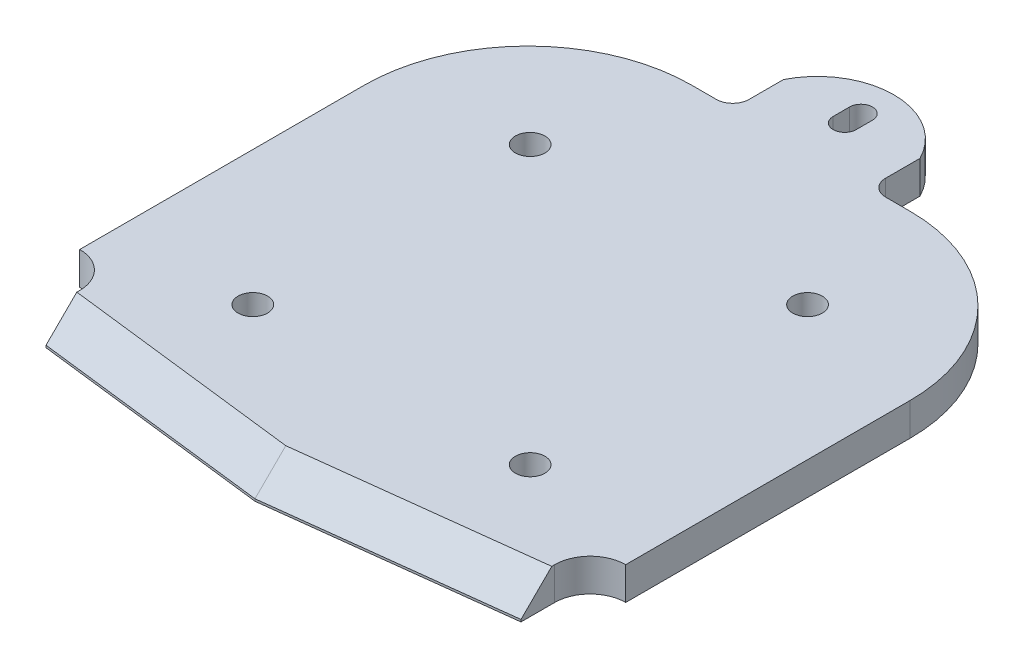
SolidWorks part; units mm, degrees
note: The reader was unsure of these and kept them because the rebuilt part matched: shared geometry of "Sketch2<2>".
ref_plane "Front Plane" through (0, 0, 0) normal (0, 0, 1) x (1, 0, 0)
ref_plane "Top Plane" through (0, 0, 0) normal (0, 1, 0) x (1, 0, 0)
ref_plane "Right Plane" through (0, 0, 0) normal (1, 0, 0) x (0, 0, -1)
sketch "Sketch1" plane through (0, 0, 0) normal (0, 1, 0) x (1, 0, 0)
  line L0 (-12.5, 103) -> (-12.5, 109.3048)
  line L1 (12.5, 103) -> (12.5, 109.3048)
  line L2 (50, 70) -> (50, 17.9)
  line L3 (43.5, 11.4) -> (43.5, 5.2217)
  line L4 (43.5, 5.2217) -> (0, 0)
  line L5 (0, 0) -> (-43.5, 5.2217)
  line L6 (-43.5, 5.2217) -> (-43.5, 11.4)
  line L7 (-20, 100) -> (-15.5, 100)
  line L8 (-50, 17.9) -> (-50, 70)
  line L11 (0, 108) -> (0, 111) construction
  line L12 (-2.1, 108) -> (-2.1, 111)
  line L13 (2.1, 108) -> (2.1, 111)
  line L14 (-113.8555, 0) -> (97.1738, 0) construction
  line L15 (0, -54.054) -> (0, 149.2796) construction
  line L16 (15.5, 100) -> (20, 100)
  arc A0 (-15.5, 100) -> (-12.5, 103) centre (-15.5, 103) ccw
  arc A1 (12.5, 109.3048) -> (-12.5, 109.3048) centre (0, 103) ccw
  arc A2 (12.5, 103) -> (15.5, 100) centre (15.5, 103) ccw
  arc A3 (50, 70) -> (20, 100) centre (20, 70) ccw
  arc A4 (-50, 70) -> (-20, 100) centre (-20, 70) cw
  arc A5 (50, 17.9) -> (43.5, 11.4) centre (50, 11.4) ccw
  arc A6 (-43.5, 11.4) -> (-50, 17.9) centre (-50, 11.4) ccw
  arc A10 (-2.1, 108) -> (2.1, 108) centre (0, 108) ccw
  arc A11 (2.1, 111) -> (-2.1, 111) centre (0, 111) ccw
  point P31 (50, 100)
  point P34 (0, 109.5)
  point P46 (-50, 100)
  dimension "D12" = 3
  dimension "D13" = 14
  dimension "D16" = 30
  dimension "D1" = 3
  dimension "D2" = 4.2
  dimension "D3" = 109.5
  dimension "D5" = 6.845
  dimension "D6" = 6.845
  dimension "D4" = 87
  dimension "D7" = 43.5
  dimension "D10" = 100
  dimension "D11" = 50
  dimension "D8" = 11.4
  dimension "D9" = 100
  dimension "D14" = 25
  dimension "D15" = 103
extrude "Boss-Extrude1" add sketch "Sketch1" along normal blind 6 contours A6 L6 L5 L4 L3 A5 L2 A3 L16 A2 L1 A1 L0 A0 L7 A4 L8 A11 L13 A10 L12
sketch "Sketch2" plane through (0, 0, 0) normal (1, 0, 0) x (0, 0, -1)
  line L0 (5.6402, 6) -> (0, 0.4)
  line L1 (0, 0.4) -> (0, 6)
  line L2 (0, 6) -> (5.6402, 6)
  line L3 (5.2217, 6) -> (0, 6) construction
  line L4 (0, 6) -> (0, 0) construction
  line L5 (11.4, 6) -> (5.2217, 6) construction
  dimension "D1" = 0.4
  dimension "D2" = 45.205
extrude "Cut-Extrude1" cut sketch "Sketch2" along direction (-0.9929, 0, 0.1192) on the side of the normal up to next (43.5 mm away)
extrude "Cut-Extrude2" cut sketch "Sketch2<2>" along direction (-0.9929, 0, -0.1192) on the side against the normal up to next (43.5 mm away)
sketch "Sketch2<2>" plane through (0, 0, 0) normal (1, 0, 0) x (0, 0, -1) same geometry as "Sketch2"
hole_wizard "1/4-28 Tapped Hole1" positions "Sketch3" profile "Sketch4" tap size "1/4-28" standard "ANSI Inch" end condition through all
sketch "Sketch3" plane through (0, 6, 0) normal (0, 1, 0) x (1, 0, 0)
  point P1 (-25.4, 75.8)
  point P4 (25.4, 75.8)
  point P7 (25.4, 25)
  point P10 (-25.4, 25)
  dimension "D1" = 50.8
  dimension "D2" = 50.8
  dimension "D3" = 25.4
  dimension "D4" = 25
sketch "Sketch4" plane through (-25.4, 6, -75.8) normal (1, 0, 0) x (0, 0, 1)
  line L0 (0, 0) -> (0, 6)
  line L1 (0, 6) -> (2.7051, 6)
  line L2 (2.7051, 6) -> (2.7051, 0)
  line L5 (2.7051, 0) -> (0, 0)
  line L11 (0, -6.35) -> (0, 107.95) construction
  dimension "Thru Tap Drill Dia." = 5.4102
  dimension "Thru Tap Drill Depth" = 6
cosmetic thread "Hole Thread1" parameters "D2"=6.35
cosmetic thread "Hole Thread2" parameters "D2"=6.35
cosmetic thread "Hole Thread3" parameters "D2"=6.35
cosmetic thread "Hole Thread4" parameters "D2"=6.35
equation "\"D6@Sketch1\"=\"D5@Sketch1\""
equation "\"D7@Sketch1\"=\"D4@Sketch1\"/2"
equation "\"D11@Sketch1\"=\"D10@Sketch1\"/2"
equation "\"D3@Sketch3\"=\"D2@Sketch3\"/2"
